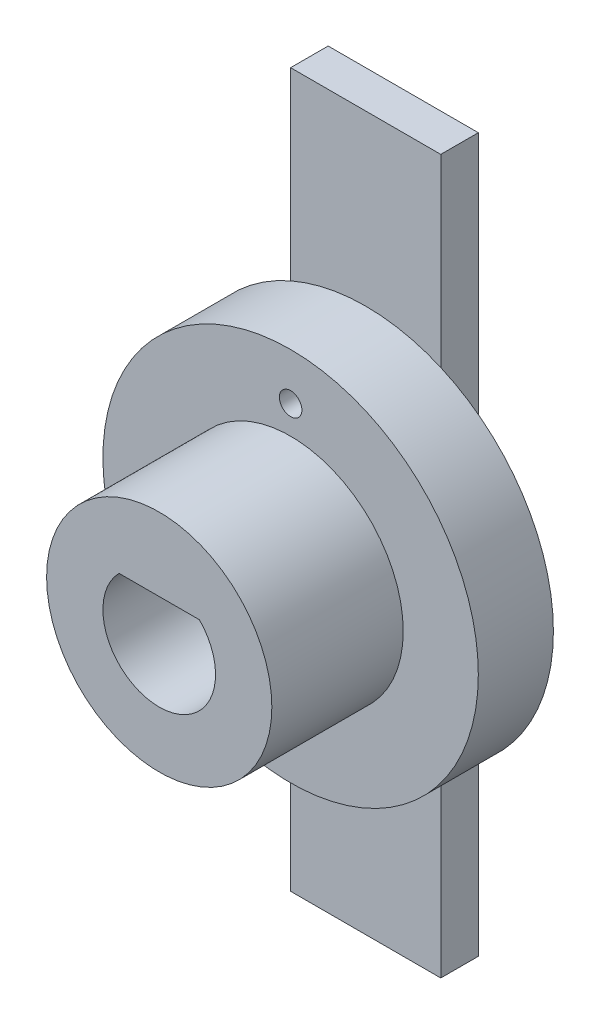
SolidWorks part; units mm, degrees
ref_plane "Plan de face" through (0, 0, 0) normal (0, 0, 1) x (1, 0, 0)
ref_plane "Plan de dessus" through (0, 0, 0) normal (0, 1, 0) x (1, 0, 0)
ref_plane "Plan de droite" through (0, 0, 0) normal (1, 0, 0) x (0, 0, -1)
sketch "Esquisse1" plane through (0, 0, 0) normal (0, 0, 1) x (1, 0, 0)
  line L8 (0, -7.5) -> (0, 7.5) construction
  circle A2 centre (0, -7.5) radius 0.6
  circle A3 centre (0, 7.5) radius 0.6
  circle A4 centre (0, 0) radius 10
  point P6 (0, 0)
  dimension "D2" = 1.2
  dimension "D3" = 1.2
  dimension "D4" = 20
  dimension "D1" = 15
extrude "Boss.-Extru.1" add sketch "Esquisse1" along normal blind 4
sketch "Esquisse2" [suppressed] plane through (0, 0, 10) normal (0, 0, 1) x (1, 0, 0)
  line L0 (-2.2, -2.0396) -> (-2.2, 2.0396)
  line L1 (3, -1.1913) -> (3, 1.3119) construction
  arc A0 (-2.2, -2.0396) -> (-2.2, 2.0396) centre (0, 0) ccw
  dimension "D1" = 6
  dimension "D2" = 5.2
extrude "Enlèv. mat.-Extru.1" [suppressed] cut sketch "Esquisse2" against normal offset from surface (8 mm away) 2 up to face at (10, 0, 0)
sketch "Esquisse3" plane through (0, 0, 4) normal (0, 0, 1) x (1, 0, 0)
  line L0 (-2.1424, 2.1) -> (2.1424, 2.1)
  line L1 (-0.8426, -3) -> (1.2459, -3) construction
  circle A0 centre (0, 0) radius 6
  arc A1 (-2.1424, 2.1) -> (2.1424, 2.1) centre (0, 0) ccw
  dimension "D1" = 6
  dimension "D3" = 12
  dimension "D2" = 5.1
extrude "Boss.-Extru.2" add sketch "Esquisse3" along normal blind 7
sketch "Esquisse4" plane through (0, 0, 0) normal (0, 0, -1) x (-1, 0, 0)
  line L1 (-4, 19) -> (4, 19)
  line L2 (-4, 19) -> (-4, -19)
  line L3 (-4, -19) -> (4, -19)
  line L4 (4, 19) -> (4, -19)
  point P4 (0, 19)
  point P5 (-4, 0)
  dimension "D1" = 8
  dimension "D2" = 38
extrude "Boss.-Extru.3" add sketch "Esquisse4" along normal blind 2
